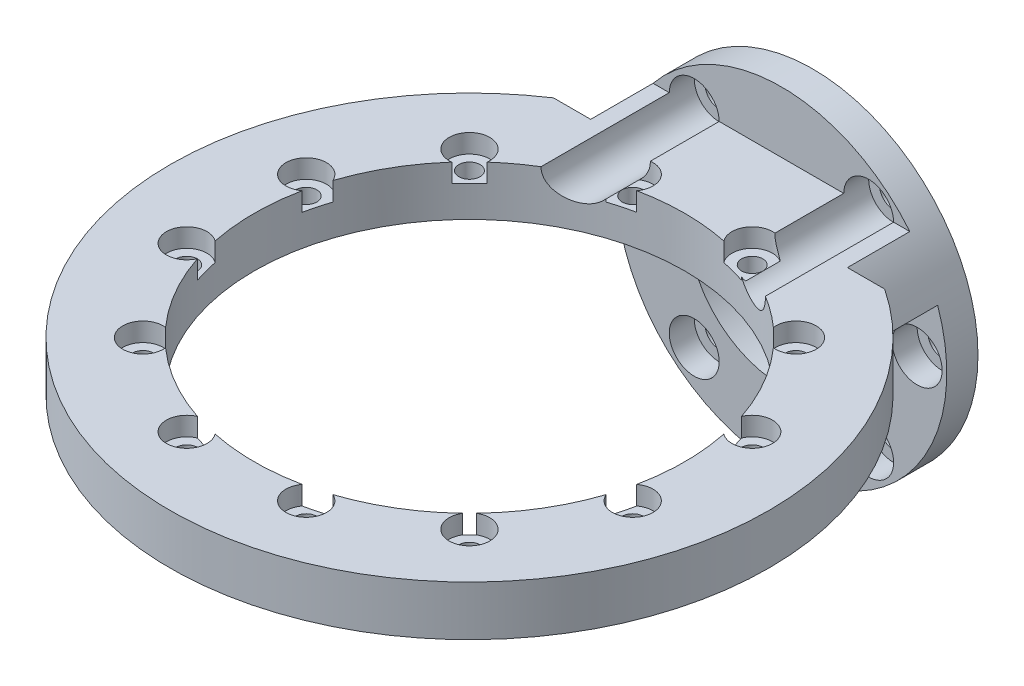
SolidWorks part; units mm, degrees
ref_plane "前视基准面" through (0, 0, 0) normal (0, 0, 1) x (1, 0, 0)
ref_plane "上视基准面" through (0, 0, 0) normal (0, 1, 0) x (1, 0, 0)
ref_plane "右视基准面" through (0, 0, 0) normal (1, 0, 0) x (0, 0, -1)
sketch "草图1" plane through (0, 0, 0) normal (0, 0, 1) x (1, 0, 0)
  circle A3 centre (0, 0) radius 26.5
extrude "凸台-拉伸1" add sketch "草图1" along normal blind 5
hole_wizard "M4 六角凹头盖的柱孔1" positions "3D草图2" profile "草图3" counterbore size "M4" standard "BSI" end condition through all
sketch3d "3D草图2"
  point P14 (-13.9806, 16.6615, 0)
  point P34 (-13.9806, 16.6615, 5)
  point P36 (13.9806, 16.6615, 5)
  point P38 (-21.75, 0, 5)
  point P40 (-13.9806, -16.6615, 5)
  point P42 (13.9806, -16.6615, 5)
  point P44 (21.75, 0, 5)
sketch "草图3" plane through (21.75, 0, 5) normal (1, 0, 0) x (0, -1, 0)
  line L0 (0, 0) -> (0, 5)
  line L1 (0, 5) -> (2.25, 5)
  line L3 (2.25, 5) -> (2.25, 4)
  line L4 (2.25, 4) -> (4, 4)
  line L5 (4, 4) -> (4, 0)
  line L7 (4, 0) -> (0, 0)
  line L11 (0, -6.35) -> (0, 107.95) construction
  dimension "通孔孔直径" = 4.5
  dimension "通孔孔深度" = 5
  dimension "柱形沉头孔直径" = 8
  dimension "柱形沉头孔深度" = 4
ref_plane "基准面1" through (0, 0, 5) normal (0, 0, 1) x (1, 0, 0)
sketch "参考" plane through (0, 0, 5) normal (0, 0, 1) x (1, 0, 0)
  line L12 (-20.7304, 8.7) -> (19.3146, 8.7) construction
ref_plane "基准面3" through (0, 8.7, 0) normal (0, -1, 0) x (1, 0, 0)
sketch "草图5" plane through (0, 8.7, 0) normal (0, -1, 0) x (1, 0, 0)
  line L0 (-26.5, 5) -> (-26.5, 14.9781)
  line L4 (26.5, 5) -> (26.5, 14.9781)
  line L9 (-26.5, 5) -> (26.5, 5)
  arc A4 (26.5, 14.9781) -> (-26.5, 14.9781) centre (0, 55) ccw
extrude "盘面" add sketch "草图5" against normal blind 8
sketch "草图6" plane through (0, 0, 5) normal (0, 0, 1) x (1, 0, 0)
  circle A0 centre (-13.9806, 16.6615) radius 4
  circle A1 centre (13.9806, 16.6615) radius 4
extrude "螺孔" cut sketch "草图6" along normal blind 22
sketch "草图8" plane through (0, 8.7, 0) normal (0, -1, 0) x (1, 0, 0)
  circle A1 centre (0, 55) radius 34.5
extrude "盘面切割" cut sketch "草图8" against normal through all
hole_wizard "M3 六角凹头盖的柱孔1" positions "3D草图3" profile "草图10" counterbore size "M3" standard "BSI" end condition through all
sketch3d "3D草图3"
  line L0 (0, 16.7, 55) -> (0, 8.7, 55) construction
  line L5 (0, 16.7, 55) -> (9.5763, 16.7, 19.2607)
  line L7 (0, 16.7, 55) -> (-9.5763, 16.7, 90.7393)
  line L11 (26.163, 16.7, 28.837) -> (0, 16.7, 55)
  line L17 (35.7393, 16.7, 45.4237) -> (0, 16.7, 55)
  line L19 (0, 16.7, 55) -> (35.7393, 16.7, 64.5763)
  line L21 (0, 16.7, 55) -> (26.6194, 16.7, 81.6194)
  line L22 (0, 16.7, 55) -> (-26.163, 16.7, 28.837)
  line L37 (0, 16.7, 55) -> (9.5763, 16.7, 90.7393)
  line L44 (-9.5763, 16.7, 19.2607) -> (0, 16.7, 55)
  line L54 (0, 16.7, 55) -> (-35.7393, 16.7, 45.4237)
  line L56 (0, 16.7, 55) -> (-26.163, 16.7, 81.163)
  line L68 (0, 16.7, 55) -> (-35.7393, 16.7, 64.5763)
  point P19 (9.5763, 16.7, 19.2607)
  point P34 (26.163, 16.7, 28.837)
  point P43 (35.7393, 16.7, 45.4237)
  point P46 (35.7393, 16.7, 64.5763)
  point P49 (26.6194, 16.7, 81.6194)
  point P169 (9.5763, 16.7, 90.7393)
  point P171 (-9.5763, 16.7, 90.7393)
  point P173 (-26.163, 16.7, 81.163)
  point P181 (-26.163, 16.7, 28.837)
  point P183 (-35.7393, 16.7, 45.4237)
  point P185 (-35.7393, 16.7, 64.5763)
  point P187 (-9.5763, 16.7, 19.2607)
sketch "草图10" plane through (-9.5763, 16.7, 19.2607) normal (1, 0, 0) x (0, 0, 1)
  line L0 (0, 0) -> (0, 43.2)
  line L1 (0, 43.2) -> (1.7, 43.2)
  line L3 (1.7, 43.2) -> (1.7, 3)
  line L4 (1.7, 3) -> (3.25, 3)
  line L5 (3.25, 3) -> (3.25, 0)
  line L7 (3.25, 0) -> (0, 0)
  line L11 (0, -6.35) -> (0, 107.95) construction
  dimension "通孔孔直径" = 3.4
  dimension "通孔孔深度" = 43.2
  dimension "柱形沉头孔直径" = 6.5
  dimension "柱形沉头孔深度" = 3
sketch "草图11" plane through (0, 0, 0) normal (0, 0, 1) x (1, 0, 0)
  line L0 (-25.0312, 8.7) -> (-29.0312, 8.7)
  line L1 (-19.36, 8.7) -> (19.36, 8.7) construction
  line L2 (-29.0312, 8.7) -> (-29.0312, 16.7)
  line L3 (48, 16.7) -> (-48, 16.7) construction
  line L4 (-29.0312, 16.7) -> (-20.5757, 16.7)
  line L6 (29.0312, 16.7) -> (20.5757, 16.7)
  line L7 (29.0312, 8.7) -> (29.0312, 16.7)
  line L8 (25.0312, 8.7) -> (29.0312, 8.7)
  arc A0 (-25.0312, 8.7) -> (25.0312, 8.7) centre (0, 0) ccw construction
  arc A1 (-25.0312, 8.7) -> (-20.5757, 16.7) centre (0, 0) cw
  arc A2 (25.0312, 8.7) -> (20.5757, 16.7) centre (0, 0) ccw
extrude "切除-拉伸1" cut sketch "草图11" along normal blind 15
sketch "草图12" plane through (0, 8.7, 0) normal (0, -1, 0) x (1, 0, 0)
  line L2 (39.2995, 79.0331) -> (30.6404, 73.9927)
  line L3 (40.2995, 32.8878) -> (31.6288, 37.8938)
  line L5 (25.4094, 16.6939) -> (19.8988, 25.0014)
  line L6 (39.2995, 31.1557) -> (30.6288, 36.1618)
  line L7 (31.6038, 72.2393) -> (40.2207, 77.2552)
  line L9 (-1, 96.0328) -> (-1, 90.9861)
  line L10 (1, 96.0328) -> (1, 101.0547)
  line L11 (1, 96.0328) -> (1, 90.9861)
  line L12 (-1, 96.0328) -> (-1, 101.0547)
  line L13 (-31.6038, 72.2393) -> (-40.2207, 77.2552)
  line L14 (-39.2995, 31.1557) -> (-30.6288, 36.1618)
  line L15 (-25.4094, 16.6939) -> (-19.8988, 25.0014)
  line L16 (-40.2995, 32.8878) -> (-31.6288, 37.8938)
  line L17 (-39.2995, 79.0331) -> (-30.6404, 73.9927)
  arc A9 (27.8489, 77.813) -> (22.813, 82.849) centre (26.6194, 81.6194) ccw
  arc A13 (12.9499, 88.5902) -> (5.5801, 90.5649) centre (9.5763, 90.7393) ccw
  arc A14 (33.5513, 42.0651) -> (35.5645, 49.4283) centre (35.7393, 45.4237) ccw
  arc A15 (35.5633, 60.5798) -> (33.59, 67.9502) centre (35.7393, 64.5763) ccw
  arc A16 (22.6075, 26.986) -> (27.9776, 32.4112) centre (26.163, 28.837) ccw
  arc A17 (12.9499, 88.5902) -> (22.813, 82.849) centre (0, 55) cw
  arc A18 (33.59, 67.9502) -> (31.6038, 72.2393) centre (0, 55) ccw
  arc A19 (35.5633, 60.5798) -> (35.5645, 49.4283) centre (0, 55) cw
  arc A20 (30.6288, 36.1618) -> (27.9776, 32.4112) centre (0, 55) cw
  arc A21 (22.6075, 26.986) -> (19.8988, 25.0014) centre (0, 55) cw
  arc A22 (5.5801, 90.5649) -> (1, 90.9861) centre (0, 55) ccw
  arc A23 (25.4094, 16.6939) -> (39.2995, 31.1557) centre (0, 55) ccw
  arc A24 (31.6288, 37.8938) -> (33.5513, 42.0651) centre (0, 55) ccw
  arc A25 (40.2995, 32.8878) -> (40.2207, 77.2552) centre (0, 55) ccw
  arc A26 (39.2995, 79.0331) -> (1, 101.0547) centre (0, 55) ccw
  arc A27 (30.6404, 73.9927) -> (27.8992, 77.8296) centre (0, 55) ccw
  arc A28 (-30.6404, 73.9927) -> (-27.8992, 77.8296) centre (0, 55) cw
  arc A29 (-39.2995, 79.0331) -> (-1, 101.0547) centre (0, 55) cw
  arc A30 (-40.2995, 32.8878) -> (-40.2207, 77.2552) centre (0, 55) cw
  arc A31 (-31.6288, 37.8938) -> (-33.5513, 42.0651) centre (0, 55) cw
  arc A32 (-25.4094, 16.6939) -> (-39.2995, 31.1557) centre (0, 55) cw
  arc A33 (-5.5801, 90.5649) -> (-1, 90.9861) centre (0, 55) cw
  arc A34 (-22.6075, 26.986) -> (-19.8988, 25.0014) centre (0, 55) ccw
  arc A35 (-30.6288, 36.1618) -> (-27.9776, 32.4112) centre (0, 55) ccw
  arc A36 (-35.5633, 60.5798) -> (-35.5645, 49.4283) centre (0, 55) ccw
  arc A37 (-33.59, 67.9502) -> (-31.6038, 72.2393) centre (0, 55) cw
  arc A38 (-12.9499, 88.5902) -> (-22.813, 82.849) centre (0, 55) ccw
  arc A39 (-22.6075, 26.986) -> (-27.9776, 32.4112) centre (-26.163, 28.837) cw
  arc A40 (-35.5633, 60.5798) -> (-33.59, 67.9502) centre (-35.7393, 64.5763) cw
  arc A41 (-33.5513, 42.0651) -> (-35.5645, 49.4283) centre (-35.7393, 45.4237) cw
  arc A42 (-12.9499, 88.5902) -> (-5.5801, 90.5649) centre (-9.5763, 90.7393) cw
  arc A43 (-27.8489, 77.813) -> (-22.813, 82.849) centre (-26.6194, 81.6194) cw
extrude "切除-拉伸2" cut sketch "草图12" against normal blind 5 contours A27 L2 A26 L10 L11 A22 A13 A17 A9 | L3 A25 L7 A18 A15 A19 A14 A24 | L5 A23 L6 A20 A16 A21 | A28 A43 A38 A42 A33 L9 L12 A29 L17 | A31 A41 A36 A40 A37 L13 A30 L16 | A34 A39 A35 L14 A32 L15 region at (19.8462, 8.7, 89.8632) region at (40.0107, 8.7, 55.079) region at (30.014, 8.7, 26.342) region at (-19.8462, 8.7, 89.8632) region at (-40.0107, 8.7, 55.079) region at (-30.014, 8.7, 26.342)
sketch "草图13" plane through (0, 0, 5) normal (0, 0, 1) x (1, 0, 0)
  line L0 (-20.7304, 8.7) -> (19.3146, 8.7) construction
  line L1 (-12.2192, 8.7) -> (12.2192, 8.7)
  arc A1 (-12.2192, 8.7) -> (12.2192, 8.7) centre (0, 0) ccw
extrude "切除-拉伸3" cut sketch "草图13" against normal blind 10
